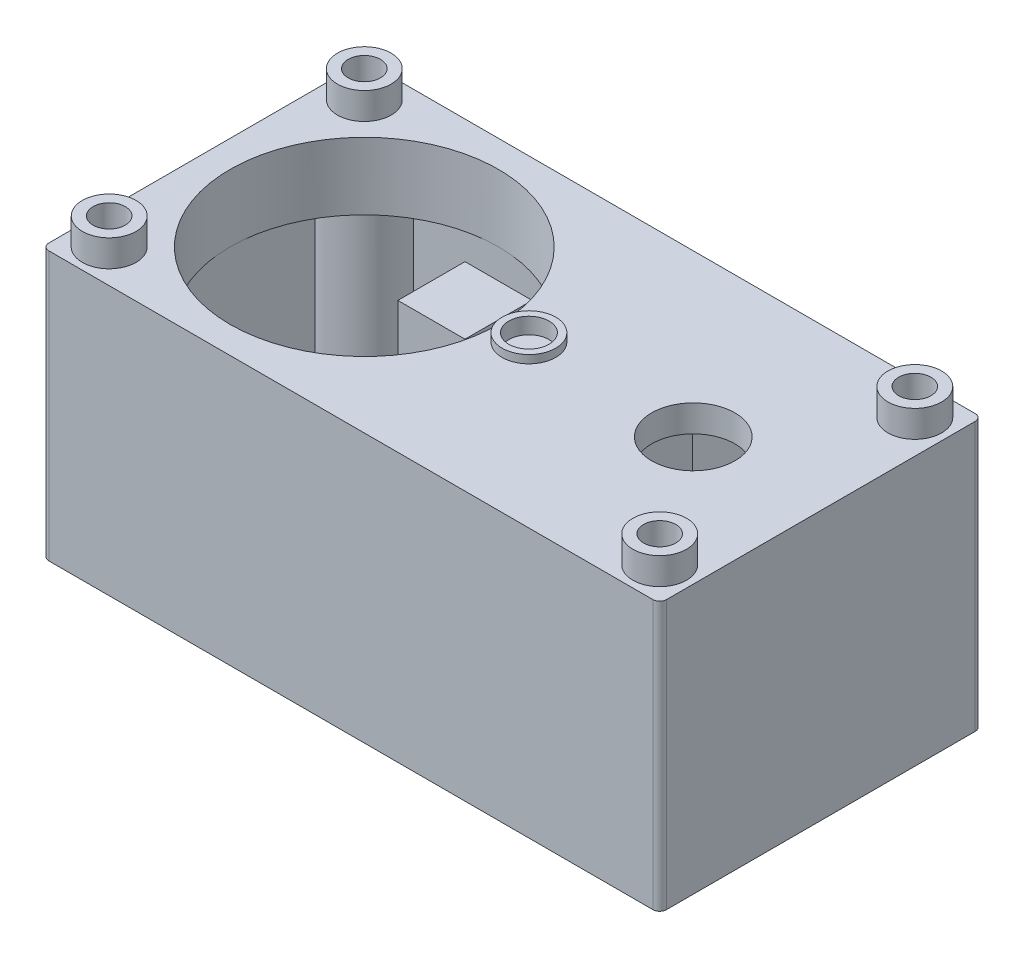
SolidWorks part; units mm, degrees
note: The reader was unsure of these and kept them because the rebuilt part matched: shared geometry of "草图1<4>", "草图2<4>", "草图2<5>".
ref_plane "前视基准面" through (0, 0, 0) normal (0, 0, 1) x (1, 0, 0)
ref_plane "上视基准面" through (0, 0, 0) normal (0, 1, 0) x (1, 0, 0)
ref_plane "右视基准面" through (0, 0, 0) normal (1, 0, 0) x (0, 0, -1)
sketch "草图1" plane through (0, 0, 0) normal (0, 1, 0) x (1, 0, 0)
  line L0 (0, 0) -> (0, -8.3295) construction
  line L1 (-11.5, 6) -> (11.5, 6)
  line L2 (-11.5, 6) -> (-11.5, -6)
  line L3 (-11.5, -6) -> (11.5, -6)
  line L4 (11.5, 6) -> (11.5, -6)
  line L5 (-11.5, 6) -> (11.5, -6) construction
  line L6 (-11.5, -6) -> (11.5, 6) construction
  circle A0 centre (-10.25, -4.75) radius 0.6
  circle A1 centre (-10.25, 4.75) radius 0.6
  circle A2 centre (10.25, -4.75) radius 0.6
  circle A3 centre (10.25, 4.75) radius 0.6
  point P0 (0, 0)
  dimension "D7" = 1.2
  dimension "D8" = 1.2
  dimension "D1" = 12
  dimension "D2" = 23
  dimension "D3" = 1.25
  dimension "D4" = 1.25
  dimension "D5" = 1.25
  dimension "D6" = 1.25
extrude "凸台-拉伸1" add sketch "草图1" along normal blind 10 contours L4 L1 L2 L3 A2 A1 A0 A3
shell "抽壳2" thickness 1
extrude "拉伸-薄壁1" add sketch "草图1<4>" along normal blind 10 from offset 1 thin contours A0 | A1 | A2 | A3
sketch "草图1<4>" plane through (0, 0, 0) normal (0, 1, 0) x (1, 0, 0) same geometry as "草图1"
sketch "草图2" plane through (0, 10, 0) normal (0, 1, 0) x (1, 0, 0)
  line L0 (11.5, 6) -> (11.5, -6) construction
  line L1 (-11.5, 6) -> (-11.5, -6) construction
  circle A0 centre (6.75, 0) radius 1.55
  circle A1 centre (-5.5, 0) radius 5
  circle A3 centre (0.63, 0) radius 0.75
  dimension "D1" = 3.1
  dimension "D3" = 10
  dimension "D5" = 1.5
  dimension "D2" = 4.75
  dimension "D4" = 6
  dimension "D6" = 6.13
extrude "切除-拉伸1" cut sketch "草图2" against normal up to next contours A1 | A0
extrude "拉伸-薄壁2" add sketch "草图2<4>" along normal blind 0.3 thin contours A3
sketch "草图2<4>" plane through (0, 10, 0) normal (0, 1, 0) x (1, 0, 0) same geometry as "草图2"
extrude "切除-拉伸2" cut sketch "草图2<5>" against normal blind 0.3 contours A3
sketch "草图2<5>" plane through (0, 10, 0) normal (0, 1, 0) x (1, 0, 0) same geometry as "草图2"
sketch "草图4" plane through (0, 9, 0) normal (0, -1, 0) x (1, 0, 0)
  line L0 (4.975, 5) -> (3.35, 3.375)
  line L1 (-8.6697, 5) -> (8.6697, 5) construction
  line L2 (3.35, 3.375) -> (3.35, -3.375)
  line L3 (3.35, -3.375) -> (4.975, -5)
  line L4 (-5.5, -5) -> (8.6697, -5) construction
  line L5 (10.5, -3.1697) -> (10.5, 3.1697) construction
  dimension "D1" = 7.15
  dimension "D2" = 135
  dimension "D3" = 135
  dimension "D4" = 6.75
extrude "拉伸-薄壁3" add sketch "草图4" along normal blind 5 thin
sketch "草图7" plane through (0, 10, 0) normal (0, 1, 0) x (1, 0, 0)
  circle A0 centre (-5.5, 0) radius 5 construction
  circle A1 centre (-5.5, 0) radius 5
extrude "拉伸-薄壁4" add sketch "草图7" against normal blind 2.5 thin
sketch "草图8" plane through (0, 10, 0) normal (0, 1, 0) x (1, 0, 0)
  line L0 (-5.5, 0) -> (-5.5, 4.4265) construction
  line L1 (-6.75, 5) -> (-4.25, 5)
  line L2 (-6.75, 5) -> (-6.75, 2.5)
  line L3 (-6.75, 2.5) -> (-4.25, 2.5)
  line L4 (-4.25, 5) -> (-4.25, 2.5)
  line L5 (-5.5, 0) -> (-7.8685, 0) construction
  line L6 (-4.25, -5) -> (-4.25, -2.5)
  line L7 (-6.75, -2.5) -> (-4.25, -2.5)
  line L8 (-6.75, -5) -> (-6.75, -2.5)
  line L9 (-6.75, -5) -> (-4.25, -5)
  circle A0 centre (-5.5, 0) radius 5 construction
  dimension "D1" = 2.5
extrude "凸台-拉伸2" add sketch "草图8" against normal blind 2.5 from offset 3.6 offset against normal yes
fillet "圆角1" radius 0.25 4 edges at (-11.5, 5, -6) (-11.5, 5, 6) (11.5, 5, -6) (11.5, 5, 6)
sketch "草图9" plane through (0, 9.7, 0) normal (0, 1, 0) x (1, 0, 0)
  arc A0 (-0.0135, -0.3852) -> (-0.0135, 0.3852) centre (0.63, 0) ccw construction
  arc A1 (-0.0135, 0.3852) -> (-0.0135, -0.3852) centre (0.63, 0) ccw construction
  arc A2 (-0.0135, -0.3852) -> (-0.0135, 0.3852) centre (0.63, 0) ccw
  arc A3 (-0.0135, 0.3852) -> (-0.0135, -0.3852) centre (0.63, 0) ccw
extrude "切除-拉伸3" cut sketch "草图9" along normal blind 2.5
